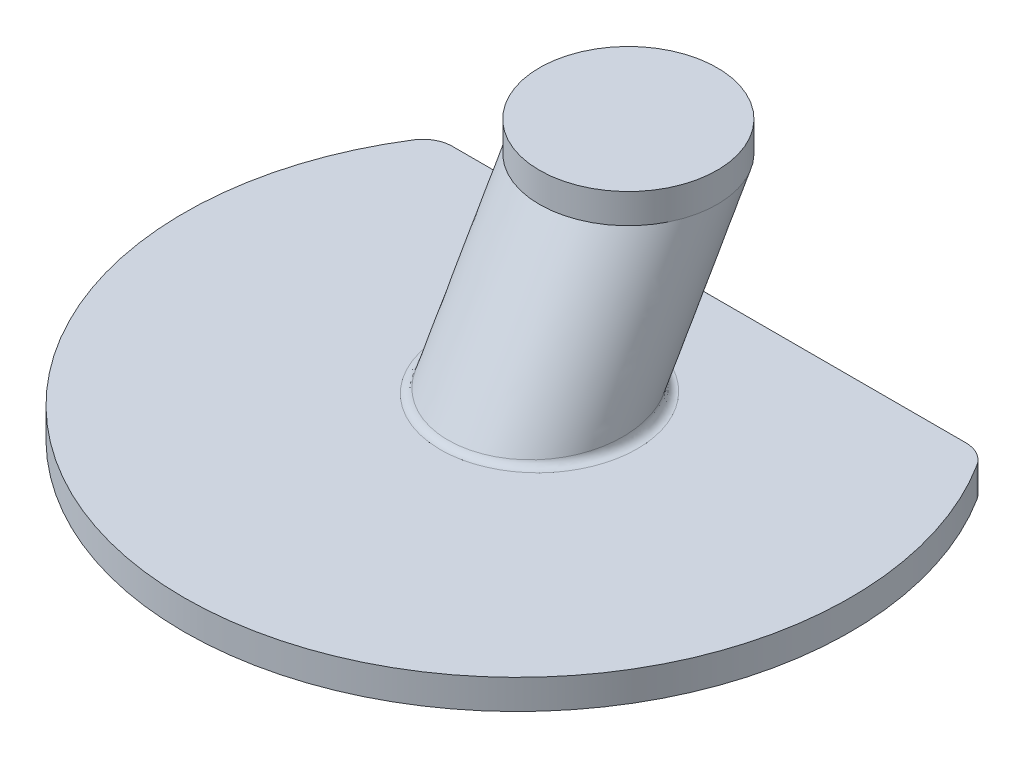
SolidWorks part; units mm, degrees
material "S-Glass Fiber"
ref_plane "Front Plane" through (0, 0, 0) normal (0, 0, 1) x (1, 0, 0)
ref_plane "Top Plane" through (0, 0, 0) normal (0, 1, 0) x (1, 0, 0)
ref_plane "Right Plane" through (0, 0, 0) normal (1, 0, 0) x (0, 0, -1)
sketch "Sketch1" plane through (0, 0, 0) normal (0, 1, 0) x (1, 0, 0)
  line L2 (86.6434, 64.7647) -> (-86.6434, 64.7647)
  arc A0 (-95.0964, 60.1076) -> (95.0964, 60.1076) centre (0, 0) ccw
  arc A1 (95.0964, 60.1076) -> (86.6434, 64.7647) centre (86.6434, 54.7647) ccw
  arc A2 (-95.0964, 60.1076) -> (-86.6434, 64.7647) centre (-86.6434, 54.7647) cw
  point P3 (-0.0631, 64.8542)
  dimension "D1" = 112.5
  dimension "D2" = 10
extrude "Boss-Extrude1" add sketch "Sketch1" along normal blind 10
sketch "Sketch4" plane through (0, 0, 0) normal (1, 0, 0) x (0, 0, -1)
  line L0 (0, 0) -> (37.5, 64.9519)
  line L1 (0, 0) -> (-44.1048, 0) construction
  point P3 (0, 0)
  dimension "D1" = 75
  dimension "D2" = 120
sketch "Sketch6" plane through (0, 0, 0) normal (0, 1, 0) x (1, 0, 0)
  circle A0 centre (0, 0) radius 30
  dimension "D1" = 60
sweep "Sweep1" add profiles "Sketch6" path "Sketch4"
fillet "Fillet1" radius 3 1 edges at (-6.9006, 10, -34.9691) type face fillet first side face at (-6.9006, 10, -34.9691) second side face at (-6.9006, 10, -34.9691)
sketch "Sketch7" plane through (0, 64.9519, 0) normal (0, 1, 0) x (1, 0, 0)
  circle A0 centre (0, 37.5) radius 30
extrude "Boss-Extrude2" add sketch "Sketch7" along normal blind 10
